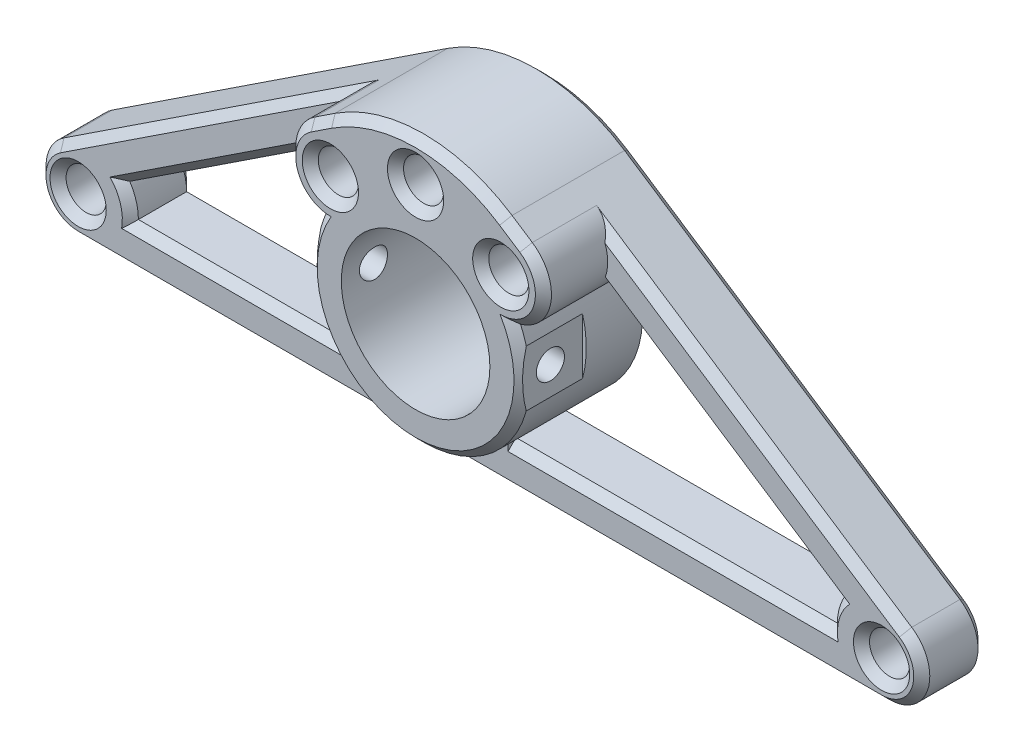
SolidWorks part; units mm, degrees
ref_plane "正面(Front)" through (0, 0, 0) normal (0, 0, 1) x (1, 0, 0)
ref_plane "平面(Top)" through (0, 0, 0) normal (0, 1, 0) x (1, 0, 0)
ref_plane "右側面(Right)" through (0, 0, 0) normal (1, 0, 0) x (0, 0, -1)
sketch "ｽｹｯﾁ1" plane through (0, 0, 0) normal (0, 0, 1) x (1, 0, 0)
  line L0 (0, 0) -> (0, -45.1659) construction
  line L1 (-50, -20) -> (50, -20)
  line L2 (52.7523, -10.8257) -> (11.0092, 16.6972)
  line L3 (-52.7523, -10.8257) -> (-11.0092, 16.6972)
  arc A0 (50, -20) -> (52.7523, -10.8257) centre (50, -15) ccw
  arc A1 (11.0092, 16.6972) -> (-11.0092, 16.6972) centre (0, 0) ccw
  arc A2 (-50, -20) -> (-52.7523, -10.8257) centre (-50, -15) cw
  circle A3 centre (0, 0) radius 9.25
  circle A4 centre (50, -15) radius 2.5
  circle A5 centre (-50, -15) radius 2.5
  point P13 (0, -20)
  dimension "D1" = 20
  dimension "D4" = 5
  dimension "D5" = 18.5
  dimension "D6" = 5
  dimension "D7" = 5
  dimension "D2" = 100
  dimension "D3" = 20
extrude "ﾎﾞｽ - 押し出し1" add sketch "ｽｹｯﾁ1" along normal blind 8
sketch "ｽｹｯﾁ2" plane through (0, 0, 8) normal (0, 0, 1) x (1, 0, 0)
  line L0 (0, 0) -> (0, 30.0608) construction
  line L1 (-10.6066, 10.6066) -> (0, 0) construction
  circle A0 centre (0, 15) radius 2.5
  circle A1 centre (-10.6066, 10.6066) radius 2.5
  arc A2 (0, 15) -> (-10.6066, 10.6066) centre (0, 0) ccw construction
  circle A3 centre (10.6066, 10.6066) radius 2.5
  dimension "D1" = 5
  dimension "D2" = 15
  dimension "D3" = 45
extrude "ｶｯﾄ - 押し出し1" cut sketch "ｽｹｯﾁ2" against normal through all
sketch "ｽｹｯﾁ3" plane through (0, 0, 8) normal (0, 0, 1) x (1, 0, 0)
  line L0 (-44.5734, -11.422) -> (-15.1981, 7.9463)
  line L2 (-43.5, -15) -> (-3.5, -15)
  line L3 (-3.5, -15) -> (-3.5, -12.7794)
  line L4 (-11.0092, 16.6972) -> (-52.7523, -10.8257) construction
  line L5 (-50, -20) -> (50, -20) construction
  line L6 (0, 0) -> (0, 27.8808) construction
  arc A0 (-12.0539, 5.5013) -> (-3.5, -12.7794) centre (0, 0) ccw
  arc A1 (-43.5, -15) -> (-44.5734, -11.422) centre (-50, -15) ccw
  circle A2 centre (0, 0) radius 9.25 construction
  arc A3 (-15.1981, 7.9463) -> (-12.0539, 5.5013) centre (-10.6066, 10.6066) ccw
  circle A4 centre (-50, -15) radius 2.5 construction
  dimension "D4" = 4
  dimension "D5" = 4
  dimension "D1" = 5
  dimension "D2" = 5
  dimension "D3" = 7
extrude "ｶｯﾄ - 押し出し2" cut sketch "ｽｹｯﾁ3" against normal through all
mirror "ﾐﾗｰ1" about plane through (0, 0, 0) normal (1, 0, 0) of "ｶｯﾄ - 押し出し2"
sketch "ｽｹｯﾁ8" plane through (0, 0, 8) normal (0, 0, 1) x (1, 0, 0)
  line L0 (-11.0092, 16.6972) -> (-52.7523, -10.8257) construction
  line L1 (-13.5276, 15.0368) -> (-11.0092, 16.6972)
  line L2 (52.7523, -10.8257) -> (11.0092, 16.6972) construction
  line L3 (11.0092, 16.6972) -> (13.5276, 15.0368)
  arc A0 (11.0092, 16.6972) -> (-11.0092, 16.6972) centre (0, 0) ccw construction
  arc A1 (12.0539, 5.5013) -> (15.1981, 7.9463) centre (10.6066, 10.6066) ccw construction
  circle A2 centre (10.6066, 10.6066) radius 2.5 construction
  circle A3 centre (0, 15) radius 2.5 construction
  circle A4 centre (-10.6066, 10.6066) radius 2.5 construction
  arc A5 (-15.1981, 7.9463) -> (-12.0539, 5.5013) centre (-10.6066, 10.6066) ccw construction
  arc A6 (3.5, -12.7794) -> (12.0539, 5.5013) centre (0, 0) ccw construction
  arc A7 (-12.0539, 5.5013) -> (-3.5, -12.7794) centre (0, 0) ccw construction
  circle A8 centre (0, 0) radius 9.25 construction
  arc A9 (11.0092, 16.6972) -> (-11.0092, 16.6972) centre (0, 0) ccw
  arc A10 (12.0539, 5.5013) -> (15.1981, 7.9463) centre (10.6066, 10.6066) ccw
  circle A11 centre (10.6066, 10.6066) radius 2.5
  circle A12 centre (0, 15) radius 2.5
  circle A13 centre (-10.6066, 10.6066) radius 2.5
  arc A14 (-15.1981, 7.9463) -> (-12.0539, 5.5013) centre (-10.6066, 10.6066) ccw
  arc A15 (3.5, -12.7794) -> (12.0539, 5.5013) centre (0, 0) ccw
  arc A16 (-12.0539, 5.5013) -> (-3.5, -12.7794) centre (0, 0) ccw
  circle A17 centre (0, 0) radius 9.25
  arc A18 (-15.1981, 7.9463) -> (-13.5276, 15.0368) centre (-10.6066, 10.6066) cw
  arc A19 (15.1981, 7.9463) -> (13.5276, 15.0368) centre (10.6066, 10.6066) ccw
  arc A20 (3.5, -12.7794) -> (-3.5, -12.7794) centre (0, 0) cw
  arc M3 (-15.1981, 7.9463) -> (-12.0539, 5.5013) centre (-10.6066, 10.6066) ccw
  arc M4 (-12.0539, 5.5013) -> (-3.5, -12.7794) centre (0, 0) ccw
  circle M9 centre (10.6066, 10.6066) radius 2.5
  circle M10 centre (-10.6066, 10.6066) radius 2.5
  circle M11 centre (0, 15) radius 2.5
  line M14 (52.7523, -10.8257) -> (11.0092, 16.6972)
  arc M15 (11.0092, 16.6972) -> (-11.0092, 16.6972) centre (0, 0) ccw
  line M16 (-11.0092, 16.6972) -> (-52.7523, -10.8257)
  circle M19 centre (0, 0) radius 9.25
  arc M21 (3.5, -12.7794) -> (12.0539, 5.5013) centre (0, 0) ccw
  arc M22 (12.0539, 5.5013) -> (15.1981, 7.9463) centre (10.6066, 10.6066) ccw
extrude "ﾎﾞｽ - 押し出し2" add sketch "ｽｹｯﾁ8" along normal blind 8 contours A20 A19 A18 M21 M22 M14 M15 M16 M3 M4 M10 M19 M11 M9 region at (-12.015, 15.4827, 8)
sketch "ｽｹｯﾁ9" plane through (0, 0, 0) normal (1, 0, 0) x (0, 0, -1)
  line L0 (-12, 15.0368) -> (-12, 9.6322) construction
  line L1 (-16, 15.0368) -> (-8, 15.0368) construction
  circle A0 centre (-12, 0) radius 1.75
  dimension "D1" = 3.5
extrude "ｶｯﾄ - 押し出し5" cut sketch "ｽｹｯﾁ9" against normal through all both and the other way through all
chamfer "面取り1" distance 1 angle 45 10 edges at (8.1066, 10.6066, 0) (2.5, 15, 0) (-8.1066, 10.6066, 0) (52.5, -15, 8) (52.5, -15, 0) (-47.5, -15, 0) (-47.5, -15, 8) (13.1066, 10.6066, 16) (2.5, 15, 16) (-8.1066, 10.6066, 16)
chamfer "面取り2" distance 1 angle 45 33 edges at (-29.8857, -1.7378, 0) (-43.7741, -13.1322, 0) (-3.5, -13.8897, 0) (-23.5, -15, 0) (29.8857, -1.7378, 0) (43.7741, -13.1322, 0) (3.5, -13.8897, 0) (23.5, -15, 0) (29.8857, -1.7378, 8) (43.7741, -13.1322, 8) (23.5, -15, 8) (-29.8857, -1.7378, 8) (-43.7741, -13.1322, 8) (-23.5, -15, 8) (54.7891, -16.4367, 0) (31.8807, 2.9358, 0) (0, -20, 0) (0, 20, 0) (-54.7891, -16.4367, 0) (-31.8807, 2.9358, 0) (-33.1399, 2.1055, 8) (33.1399, 2.1055, 8) (-54.7891, -16.4367, 8) (54.7891, -16.4367, 8) (0, -20, 8) (0, 20, 16) (-12.2684, 15.867, 16) (-15.8508, 9.7961, 16) (0, -13.25, 16) (-12.0011, -5.6156, 0) (-13.8641, 6.4177, 0) (12.0011, -5.6156, 0) (13.8641, 6.4177, 0)
sketch "ｽｹｯﾁ11" plane through (0, 0, 16) normal (0, 0, 1) x (1, 0, 0)
  line L0 (12.7794, 3.5) -> (12.7794, -3.5)
  line L1 (12.7794, -3.5) -> (15.6195, -3.5)
  line L2 (15.6195, -3.5) -> (15.6195, 3.5)
  line L3 (15.6195, 3.5) -> (12.7794, 3.5)
  line L4 (0, 0) -> (0, 15.0037) construction
  line L5 (-15.6195, -3.5) -> (-15.6195, 3.5)
  line L6 (-12.7794, -3.5) -> (-15.6195, -3.5)
  line L7 (-12.7794, 3.5) -> (-12.7794, -3.5)
  line L8 (-15.6195, 3.5) -> (-12.7794, 3.5)
  arc A0 (-12.0539, 5.5013) -> (12.0539, 5.5013) centre (0, 0) ccw construction
  dimension "D1" = 7
extrude "ｶｯﾄ - 押し出し6" cut sketch "ｽｹｯﾁ11" against normal blind 8
